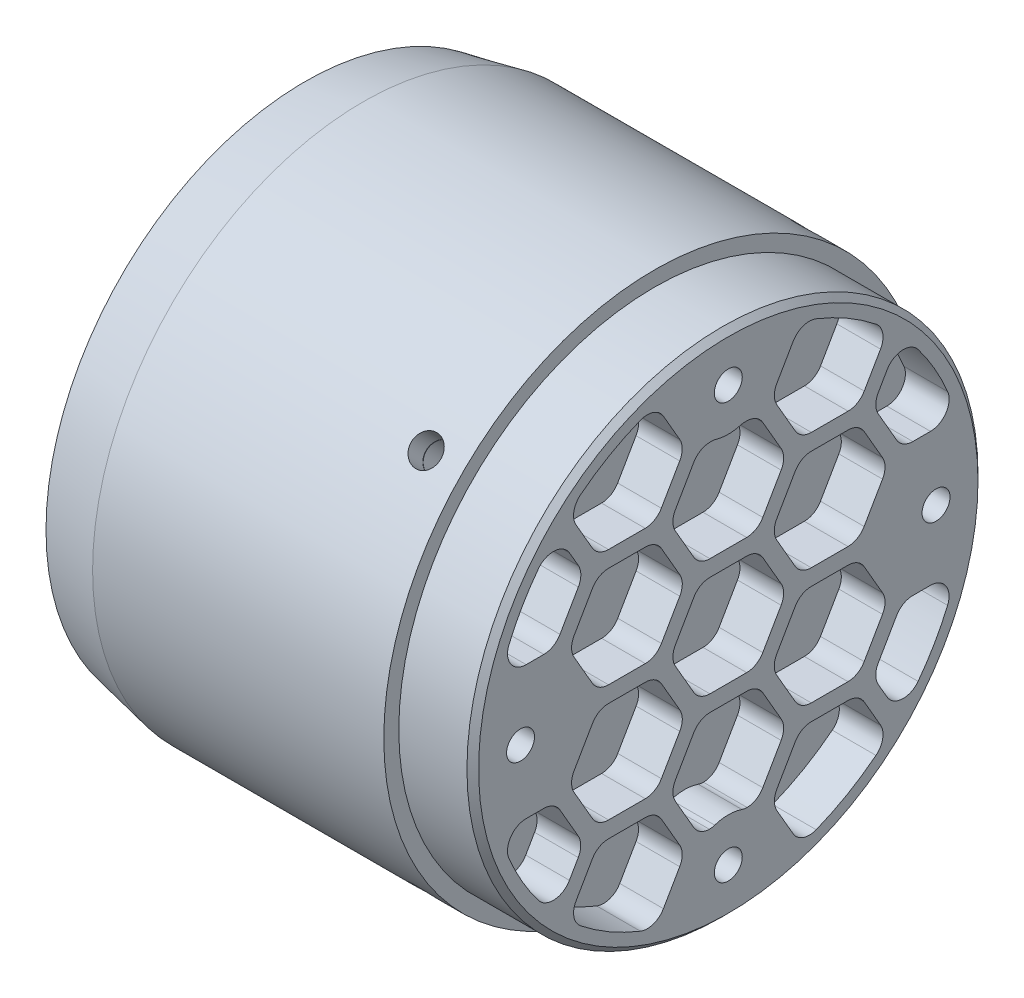
SolidWorks part; units mm, degrees
other "PC Sleeve"
other "Upper Pin Ring"
other "Lower Pin Ring"
material "6061 Alloy"
ref_plane "Front Plane" through (0, 0, 0) normal (0, 0, 1) x (1, 0, 0)
ref_plane "Top Plane" through (0, 0, 0) normal (0, 1, 0) x (1, 0, 0)
ref_plane "Right Plane" through (0, 0, 0) normal (1, 0, 0) x (0, 0, -1)
sketch "Sketch1" plane through (0, 0, 0) normal (0, 0, 1) x (1, 0, 0)
  line L0 (0, 0) -> (74.8253, 0) construction
  line L1 (10, 46.45) -> (60, 46.45)
  line L6 (0, 44.45) -> (10, 46.45)
  line L7 (0, 0) -> (0, 44.45) construction
  line L17 (60, 44.45) -> (60, 46.45)
  line L18 (60, 44.45) -> (60, 42.85)
  line L19 (60, 42.85) -> (40, 42.85)
  line L20 (40, 42.85) -> (40, 44.45)
  line L21 (40, 44.45) -> (0, 44.45)
  line L22 (40, 44.45) -> (60, 44.45) construction
  dimension "D1" = 88.9
  dimension "D2" = 60
  dimension "D3" = 10
  dimension "D4" = 20
  dimension "D5" = 2
  dimension "D6" = 1.6
revolve "Revolve1" add sketch "Sketch1" angle 360 about L0
sketch "Sketch2" plane through (0, 0, 0) normal (0, 0, 1) x (1, 0, 0)
  line L0 (0, 0) -> (60, 0) construction
  line L2 (60, -46.45) -> (60, 46.45) construction
  line L3 (60, 42.77) -> (47.3, 42.77)
  line L4 (60, 42.77) -> (60, 28.575)
  line L5 (60, 28.575) -> (47.3, 28.575)
  line L6 (47.3, 42.77) -> (47.3, 28.575)
  line L7 (60, -46.45) -> (60, 46.45) construction
  line L8 (60, 42.85) -> (0, 42.85) construction
  line L9 (0, 44.45) -> (0, -44.45) construction
  dimension "D1" = 12.7
  dimension "D2" = 28.575
  dimension "D3" = 0.08
revolve "Revolve2" add sketch "Sketch2" angle 360 about L0
sketch "Sketch3" plane through (60, 0, 0) normal (1, 0, 0) x (0, 0, -1)
  line L0 (-35.6725, 0) -> (0, 0) construction
  line L1 (0, 35.6725) -> (0, 0) construction
  line L2 (35.6725, 0) -> (0, 0) construction
  line L3 (0, -35.6725) -> (0, 0) construction
  line L4 (-28.575, 0) -> (-42.77, 0) construction
  circle A0 centre (-35.6725, 0) radius 2.45
  circle A1 centre (0, 35.6725) radius 2.45
  circle A2 centre (35.6725, 0) radius 2.45
  circle A3 centre (0, -35.6725) radius 2.45
  circle A4 centre (0, 0) radius 28.575 construction
  circle A5 centre (0, 0) radius 42.77 construction
  point P13 (0, 0)
  dimension "D1" = 4.9
  dimension "D3" = 4
extrude "Cut-Extrude1" cut sketch "Sketch3" against normal through all
ref_plane "Plane1" through (0, 32.8451, 32.8451) normal (0, 0.7071, 0.7071) x (-1, 0, 0)
sketch "Sketch4" plane through (0, 32.8451, 32.8451) normal (0, 0.7071, 0.7071) x (-1, 0, 0)
  line L0 (-53.65, 0) -> (0, 0) construction
  line L1 (-60, 46.45) -> (-60, -46.45) construction
  circle A0 centre (-53.65, 0) radius 2.54
  dimension "D1" = 5.08
  dimension "D2" = 6.35
extrude "Cut-Extrude2" cut sketch "Sketch4" against normal up to surface (17.9881 mm away) up to face at (60, 0, 28.575)
ref_axis "Axis1" through (60, 0, 0) along (-1, 0, 0)
pattern_circular "CirPattern1" count 4 over 360 about axis through (60, 0, 0) along (-1, 0, 0) of "Cut-Extrude2"
sketch "Sketch5" plane through (60, 0, 0) normal (1, 0, 0) x (0, 0, -1)
  line L0 (0, 0) -> (-20.2056, 20.2056) construction
  line L3 (0, 0) -> (0, 35.6725) construction
  line L5 (-21.9733, 11.3667) -> (-18.4378, 29.0444) construction
  line L6 (-29.0444, 18.4378) -> (-11.3667, 21.9733) construction
  line L7 (-29.0444, 18.4378) -> (-18.4378, 29.0444)
  line L8 (-18.4378, 29.0444) -> (-11.3667, 21.9733)
  line L9 (-11.3667, 21.9733) -> (-21.9733, 11.3667)
  line L10 (-21.9733, 11.3667) -> (-29.0444, 18.4378)
  circle A0 centre (0, 0) radius 28.575 construction
  point P10 (-20.2056, 20.2056)
  point P12 (-20.2056, 20.2056)
  dimension "D1" = 45
  dimension "D2" = 15
  dimension "D3" = 10
extrude "Cut-Extrude3" cut sketch "Sketch5" against normal up to surface (12.7 mm away) up to face at (47.3, 0, 33.2225)
fillet "Fillet1" radius 3.2 4 edges at (53.65, 14.1939, 24.8005) (53.65, 24.8005, 14.1939) (53.65, 18.4378, 29.0444) (53.65, 29.0444, 18.4378)
fillet "Fillet2" radius 3.2 1 edges at (40, 0, 44.45)
sketch "Sketch6" plane through (60, 0, 0) normal (1, 0, 0) x (0, 0, -1)
  circle A0 centre (0, 0) radius 43.875
  circle A1 centre (-35.6725, 0) radius 2.45 construction
  circle A2 centre (0, -35.6725) radius 2.45 construction
  circle A3 centre (35.6725, 0) radius 2.45 construction
  circle A4 centre (0, 35.6725) radius 2.45 construction
  circle A5 centre (-35.6725, 0) radius 2.45 construction
  circle A6 centre (0, -35.6725) radius 2.45 construction
  circle A7 centre (35.6725, 0) radius 2.45 construction
  circle A8 centre (0, 35.6725) radius 2.45 construction
  circle A9 centre (0, 35.6725) radius 2.4
  circle A10 centre (35.6725, 0) radius 2.4
  circle A11 centre (0, -35.6725) radius 2.4
  circle A12 centre (-35.6725, 0) radius 2.4
  dimension "D1" = 87.75
  dimension "D2" = 0.05
extrude "Boss-Extrude1" add sketch "Sketch6" along normal blind 12.7 separate body
chamfer "Chamfer1" distance 1 angle 45 1 edges at (72.7, 0, -43.875)
sketch "Sketch7" plane through (72.7, 0, 0) normal (1, 0, 0) x (0, 0, -1)
  line L0 (10, 20.0975) -> (5, 28.7578)
  line L1 (10, 0) -> (5, 8.6603)
  line L2 (5, 8.6603) -> (-5, 8.6603)
  line L3 (-5, 8.6603) -> (-10, 0)
  line L4 (-10, 0) -> (-5, -8.6603)
  line L5 (-5, -8.6603) -> (5, -8.6603)
  line L6 (5, -8.6603) -> (10, 0)
  line L7 (5, 28.7578) -> (-5, 28.7578)
  line L8 (-5, 28.7578) -> (-10, 20.0975)
  line L9 (-10, 20.0975) -> (-5, 11.4373)
  line L10 (-5, 11.4373) -> (5, 11.4373)
  line L11 (5, 11.4373) -> (10, 20.0975)
  line L12 (22.405, 1.3885) -> (27.405, 10.0488)
  line L13 (27.405, 10.0488) -> (22.405, 18.709)
  line L14 (22.405, 18.709) -> (12.405, 18.709)
  line L15 (12.405, 18.709) -> (7.405, 10.0488)
  line L16 (7.405, 10.0488) -> (12.405, 1.3885)
  line L17 (12.405, 1.3885) -> (22.405, 1.3885)
  line L18 (12.405, -18.709) -> (22.405, -18.709)
  line L19 (22.405, -18.709) -> (27.405, -10.0488)
  line L20 (27.405, -10.0488) -> (22.405, -1.3885)
  line L21 (22.405, -1.3885) -> (12.405, -1.3885)
  line L22 (12.405, -1.3885) -> (7.405, -10.0488)
  line L23 (7.405, -10.0488) -> (12.405, -18.709)
  line L24 (-10, -20.0975) -> (-5, -28.7578)
  line L25 (-5, -28.7578) -> (5, -28.7578)
  line L26 (5, -28.7578) -> (10, -20.0975)
  line L27 (10, -20.0975) -> (5, -11.4373)
  line L28 (5, -11.4373) -> (-5, -11.4373)
  line L29 (-5, -11.4373) -> (-10, -20.0975)
  line L30 (-22.405, -1.3885) -> (-27.405, -10.0488)
  line L31 (-27.405, -10.0488) -> (-22.405, -18.709)
  line L32 (-22.405, -18.709) -> (-12.405, -18.709)
  line L33 (-12.405, -18.709) -> (-7.405, -10.0488)
  line L34 (-7.405, -10.0488) -> (-12.405, -1.3885)
  line L35 (-12.405, -1.3885) -> (-22.405, -1.3885)
  line L36 (-12.405, 18.709) -> (-22.405, 18.709)
  line L37 (-22.405, 18.709) -> (-27.405, 10.0488)
  line L38 (-27.405, 10.0488) -> (-22.405, 1.3885)
  line L39 (-22.405, 1.3885) -> (-12.405, 1.3885)
  line L40 (-12.405, 1.3885) -> (-7.405, 10.0488)
  line L41 (-7.405, 10.0488) -> (-12.405, 18.709)
  line L42 (22.4182, 21.509) -> (27.4182, 30.1693)
  line L43 (-7.4182, 30.1693) -> (-12.4182, 38.8295)
  line L44 (-12.4182, 38.8295) -> (-22.4182, 38.8295)
  line L45 (-22.4182, 38.8295) -> (-27.4182, 30.1693)
  line L46 (-27.4182, 30.1693) -> (-22.4182, 21.509)
  line L47 (-22.4182, 21.509) -> (-12.4182, 21.509)
  line L48 (-12.4182, 21.509) -> (-7.4182, 30.1693)
  line L49 (27.4182, 30.1693) -> (22.4182, 38.8295)
  line L50 (22.4182, 38.8295) -> (12.4182, 38.8295)
  line L51 (12.4182, 38.8295) -> (7.4182, 30.1693)
  line L52 (7.4182, 30.1693) -> (12.4182, 21.509)
  line L53 (12.4182, 21.509) -> (22.4182, 21.509)
  line L54 (29.8365, -8.6603) -> (39.8365, -8.6603)
  line L55 (39.8365, -8.6603) -> (44.8365, 0)
  line L56 (44.8365, 0) -> (39.8365, 8.6603)
  line L57 (39.8365, 8.6603) -> (29.8365, 8.6603)
  line L58 (29.8365, 8.6603) -> (24.8365, 0)
  line L59 (24.8365, 0) -> (29.8365, -8.6603)
  line L60 (7.4182, -30.1693) -> (12.4182, -38.8295)
  line L61 (12.4182, -38.8295) -> (22.4182, -38.8295)
  line L62 (22.4182, -38.8295) -> (27.4182, -30.1693)
  line L63 (27.4182, -30.1693) -> (22.4182, -21.509)
  line L64 (22.4182, -21.509) -> (12.4182, -21.509)
  line L65 (12.4182, -21.509) -> (7.4182, -30.1693)
  line L66 (-22.4182, -21.509) -> (-27.4182, -30.1693)
  line L67 (-27.4182, -30.1693) -> (-22.4182, -38.8295)
  line L68 (-22.4182, -38.8295) -> (-12.4182, -38.8295)
  line L69 (-12.4182, -38.8295) -> (-7.4182, -30.1693)
  line L70 (-7.4182, -30.1693) -> (-12.4182, -21.509)
  line L71 (-12.4182, -21.509) -> (-22.4182, -21.509)
  line L72 (-29.8365, 8.6603) -> (-39.8365, 8.6603)
  line L73 (-39.8365, 8.6603) -> (-44.8365, 0)
  line L74 (-44.8365, 0) -> (-39.8365, -8.6603)
  line L75 (-39.8365, -8.6603) -> (-29.8365, -8.6603)
  line L76 (-29.8365, -8.6603) -> (-24.8365, 0)
  line L77 (-24.8365, 0) -> (-29.8365, 8.6603)
  line L78 (39.8232, -28.7808) -> (44.8232, -20.1205)
  line L79 (44.8365, 20.0975) -> (39.8365, 28.7578)
  line L80 (39.8365, 28.7578) -> (29.8365, 28.7578)
  line L81 (29.8365, 28.7578) -> (24.8365, 20.0975)
  line L82 (24.8365, 20.0975) -> (29.8365, 11.4373)
  line L83 (29.8365, 11.4373) -> (39.8365, 11.4373)
  line L84 (39.8365, 11.4373) -> (44.8365, 20.0975)
  line L85 (44.8232, -20.1205) -> (39.8232, -11.4603)
  line L86 (39.8232, -11.4603) -> (29.8232, -11.4603)
  line L87 (29.8232, -11.4603) -> (24.8232, -20.1205)
  line L88 (24.8232, -20.1205) -> (29.8232, -28.7808)
  line L89 (29.8232, -28.7808) -> (39.8232, -28.7808)
  line L90 (-5.0133, -48.8783) -> (4.9867, -48.8783)
  line L91 (4.9867, -48.8783) -> (9.9867, -40.218)
  line L92 (9.9867, -40.218) -> (4.9867, -31.5578)
  line L93 (4.9867, -31.5578) -> (-5.0133, -31.5578)
  line L94 (-5.0133, -31.5578) -> (-10.0133, -40.218)
  line L95 (-10.0133, -40.218) -> (-5.0133, -48.8783)
  line L96 (-44.8365, -20.0975) -> (-39.8365, -28.7578)
  line L97 (-39.8365, -28.7578) -> (-29.8365, -28.7578)
  line L98 (-29.8365, -28.7578) -> (-24.8365, -20.0975)
  line L99 (-24.8365, -20.0975) -> (-29.8365, -11.4373)
  line L100 (-29.8365, -11.4373) -> (-39.8365, -11.4373)
  line L101 (-39.8365, -11.4373) -> (-44.8365, -20.0975)
  line L102 (-39.8232, 28.7808) -> (-44.8232, 20.1205)
  line L103 (-44.8232, 20.1205) -> (-39.8232, 11.4603)
  line L104 (-39.8232, 11.4603) -> (-29.8232, 11.4603)
  line L105 (-29.8232, 11.4603) -> (-24.8232, 20.1205)
  line L106 (-24.8232, 20.1205) -> (-29.8232, 28.7808)
  line L107 (-29.8232, 28.7808) -> (-39.8232, 28.7808)
  line L108 (5.0133, 48.8783) -> (-4.9867, 48.8783)
  line L109 (-4.9867, 48.8783) -> (-9.9867, 40.218)
  line L110 (-9.9867, 40.218) -> (-4.9867, 31.5578)
  line L111 (-4.9867, 31.5578) -> (5.0133, 31.5578)
  line L112 (5.0133, 31.5578) -> (10.0133, 40.218)
  line L113 (10.0133, 40.218) -> (5.0133, 48.8783)
  circle A0 centre (0, 0) radius 8.6603 construction
  circle A1 centre (-35.6725, 0) radius 2.45 construction
  circle A2 centre (-17.4182, 30.1693) radius 8.6603 construction
  circle A3 centre (34.8365, 20.0975) radius 8.6603 construction
  circle A4 centre (0, 35.6725) radius 2.4 construction
  circle A7 centre (0, 0) radius 40.875
  circle A8 centre (0, 0) radius 40.875
  circle A32 centre (0, -35.6725) radius 7.45
  circle A35 centre (-35.6725, 0) radius 7.45
  circle A38 centre (0, 35.8095) radius 7.45
  circle A41 centre (35.6725, 0) radius 7.45
  point P49 (0, 0)
  point P89 (0, 0)
  point P127 (0, 0)
  dimension "D15" = 14.9
  dimension "D1" = 10
  dimension "D3" = 4.9867
  dimension "D4" = 6
  dimension "D5" = 2.8
  dimension "D6" = 2.8
  dimension "D8" = 5.0133
  dimension "D9" = 2.8
  dimension "D10" = 2.8
  dimension "D11" = 6
  dimension "D12" = 24.8232
  dimension "D13" = 4.5455
  dimension "D14" = 2
  dimension "D16" = 35.6725
  dimension "D17" = 35.6725
  dimension "D18" = 0.137
  dimension "D19" = 35.6725
  dimension "D20" = 71.345
  dimension "D2" = 2
  dimension "D7" = 6
extrude "Cut-Extrude4" cut sketch "Sketch7" against normal blind 7.5 contours L44 A8 L45 L46 L47 L48 L43 | L106 A8 L104 L105 | L100 A8 L98 L99 | L34 L35 L30 L31 L32 L33 | L40 L41 L36 L37 L38 L39 | A38 L7 L8 L9 L10 L11 L0 | L49 A8 L50 L51 L52 L53 L42 | L83 A8 L81 L82 | L16 L17 L12 L13 L14 L15 | L5 L6 L1 L2 L3 L4 | L22 L23 L18 L19 L20 L21 | A32 L25 L26 L27 L28 L29 L24 | L67 A8 L68 L69 L70 L71 L66 | L61 A8 L62 L63 L64 L65 L60 | L88 A8 L86 L87 region at (72.7, 20.0553, 0) region at (72.7, 29.3367, -16.9375) region at (72.7, 29.3367, 16.9375) region at (72.7, 18.2538, -31.6401) region at (72.7, 18.2742, 31.6283) region at (72.7, -18.2742, -31.6283) region at (72.7, -18.2538, 31.6401) region at (72.7, -29.3367, -16.9375) region at (72.7, -29.3367, 16.9375) region at (72.7, -20.0322, 0) region at (72.7, 0, 0) region at (72.7, 10.0488, -17.405) region at (72.7, -10.0488, -17.405) region at (72.7, -10.0488, 17.405) region at (72.7, 10.0488, 17.405)
fillet "Fillet3" radius 3.2 79 edges at (68.95, 11.4373, -39.2422) (68.95, 28.2489, -29.5426) (68.95, 20.0975, -24.8365) (68.95, 11.4373, -29.8365) (68.95, 38.8295, -12.4182) (68.95, 30.4726, -27.2431) (68.95, 21.509, -22.4182) (68.95, 21.509, -12.4182) (68.95, 30.1693, -7.4182) (68.95, 1.3885, -12.405) (68.95, 1.3885, -22.405) (68.95, 10.0488, -27.405) (68.95, 18.709, -22.405) (68.95, 18.709, -12.405) (68.95, 10.0488, -7.405) (68.95, -10.0488, -27.405) (68.95, -1.3885, -22.405) (68.95, -1.3885, -12.405) (68.95, -10.0488, -7.405) (68.95, -18.709, -22.405) (68.95, -18.709, -12.405) (68.95, -11.4603, -39.2355) (68.95, -11.4603, -29.8232) (68.95, -20.1205, -24.8232) (68.95, -28.2661, -29.5261) (68.95, -38.8295, -12.4182) (68.95, -21.509, -22.4182) (68.95, -30.1693, -27.4182) (68.95, -21.509, -12.4182) (68.95, -30.1693, -7.4182) (68.95, -20.0975, -10) (68.95, -11.4373, -5) (68.95, -11.4373, 5) (68.95, -20.0975, 10) (68.95, -28.7578, 5) (68.95, -28.7578, 2.773) (68.95, -28.7578, -2.773) (68.95, -28.7578, -5) (68.95, -28.2489, 29.5426) (68.95, -30.1693, 27.4182) (68.95, -21.509, 22.4182) (68.95, -21.509, 12.4182) (68.95, -30.1693, 7.4182) (68.95, -38.8295, 12.4182) (68.95, -1.3885, 22.405) (68.95, -10.0488, 27.405) (68.95, -18.709, 22.405) (68.95, -18.709, 12.405) (68.95, -10.0488, 7.405) (68.95, -1.3885, 12.405) (68.95, 0, -10) (68.95, 8.6603, -5) (68.95, -8.6603, -5) (68.95, -8.6603, 5) (68.95, 8.6603, 5) (68.95, 0, 10) (68.95, 11.4373, 5) (68.95, 20.0975, 10) (68.95, 11.4373, -5) (68.95, 20.0975, -10) (68.95, 28.7578, -5) (68.95, 28.7578, -2.4032) (68.95, 28.7578, 2.4032) (68.95, 28.7578, 5) (68.95, 30.4726, 27.2431) (68.95, 38.8295, 12.7684) (68.95, 30.1693, 7.4182) (68.95, 21.509, 12.4182) (68.95, 21.509, 22.4182) (68.95, 10.0488, 7.405) (68.95, 1.3885, 22.405) (68.95, 1.3885, 12.405) (68.95, 18.709, 12.405) (68.95, 18.709, 22.405) (68.95, 10.0488, 27.405) (68.95, 11.4603, 29.8232) (68.95, 20.1205, 24.8232) (68.95, 11.4603, 39.2355) (68.95, 28.2661, 29.5261)
fillet "Fillet4" radius 3.2 11 edges at (68.95, 30.1693, 27.4182) (68.95, 38.8295, 12.4182) (68.95, -30.4726, 27.2431) (68.95, -38.8295, 12.7684) (68.95, -11.4373, 39.2422) (68.95, -20.0975, 24.8365) (68.95, -11.4373, 29.8365) (68.95, -38.8295, -12.7684) (68.95, -30.4726, -27.2431) (68.95, 38.8295, -12.7684) (68.95, 30.1693, -27.4182)
